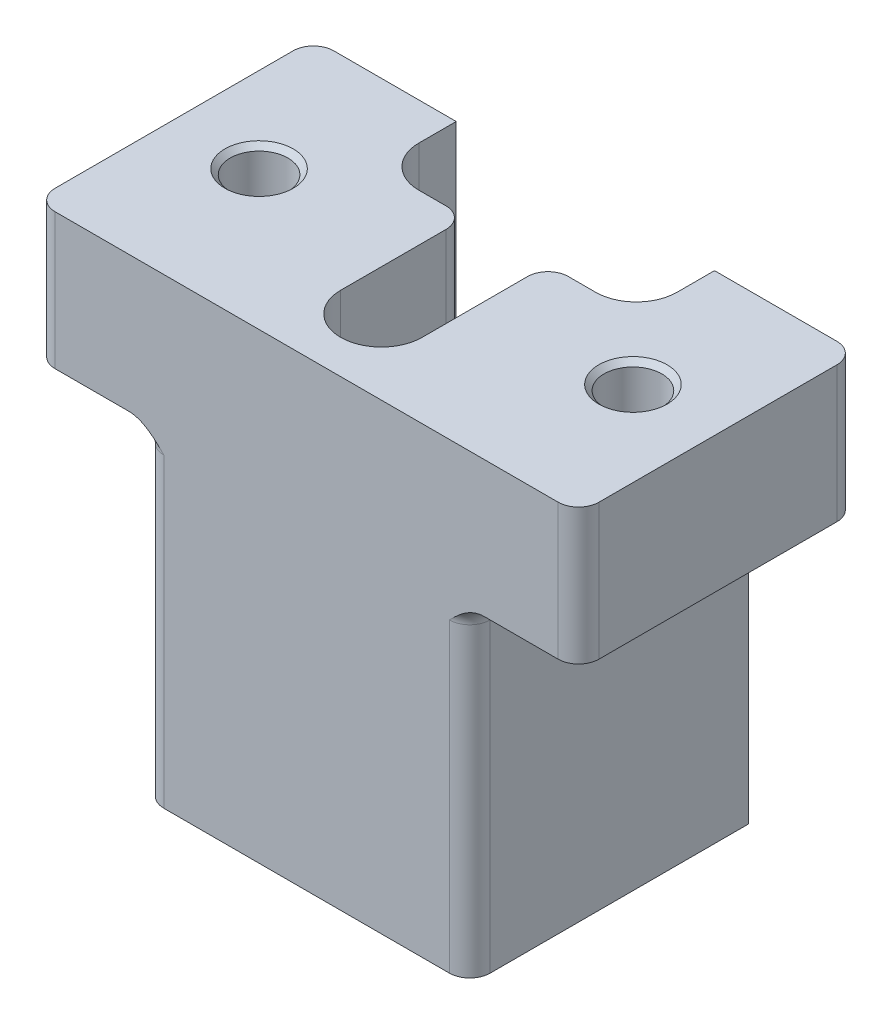
SolidWorks part; units mm, degrees
material "K110"
ref_plane "Front Plane" through (0, 0, 0) normal (0, 0, 1) x (1, 0, 0)
ref_plane "Top Plane" through (0, 0, 0) normal (0, 1, 0) x (1, 0, 0)
ref_plane "Right Plane" through (0, 0, 0) normal (1, 0, 0) x (0, 0, -1)
sketch "Sketch2" plane through (0, 0, 0) normal (0, 1, 0) x (1, 0, 0)
  line L0 (-19, 19.87) -> (-37, 19.87) construction
  line L1 (-40, -21.13) -> (40, -21.13)
  line L2 (-40, -21.13) -> (-40, 19.87)
  line L3 (-40, 19.87) -> (40, 19.87)
  line L4 (40, -21.13) -> (40, 19.87)
  line L5 (0, 0) -> (0, 19.87) construction
  line L7 (-37, -21.13) -> (37, -21.13) construction
  dimension "D2" = 80
extrude "Boss-Extrude1" add sketch "Sketch2" against normal blind 68
fillet "Fillet1" radius 3 4 edges at (-40, -34, -19.87) (-40, -34, 21.13) (40, -34, -19.87) (40, -34, 21.13)
sketch "Sketch5" plane through (0, -68, 0) normal (0, -1, 0) x (1, 0, 0)
  line L0 (19, -19.87) -> (24, -19.87) construction
  line L1 (19, -14.37) -> (19, -19.87) construction
  line L2 (9, -8.37) -> (13, -8.37) construction
  line L3 (6, 10.13) -> (6, -5.37) construction
  line L4 (-6, -5.37) -> (-6, 10.13) construction
  line L5 (-13, -8.37) -> (-9, -8.37) construction
  line L6 (-19, -19.87) -> (-19, -14.37) construction
  line L7 (-24, -19.87) -> (-19, -19.87) construction
  line L8 (-24, -19.87) -> (-24, 21.13) construction
  line L9 (24, 21.13) -> (-24, 21.13) construction
  line L10 (24, -19.87) -> (24, 21.13) construction
  line L11 (19, -19.87) -> (24, -19.87)
  line L12 (19, -14.37) -> (19, -19.87)
  line L13 (9, -8.37) -> (13, -8.37)
  line L14 (6, 10.13) -> (6, -5.37)
  line L15 (-6, -5.37) -> (-6, 10.13)
  line L16 (-13, -8.37) -> (-9, -8.37)
  line L17 (-19, -19.87) -> (-19, -14.37)
  line L18 (-24, -19.87) -> (-19, -19.87)
  line L19 (-24, -19.87) -> (-24, 21.13)
  line L20 (24, 21.13) -> (-24, 21.13)
  line L21 (24, -19.87) -> (24, 21.13)
  arc A0 (19, -14.37) -> (13, -8.37) centre (13, -14.37) ccw construction
  arc A1 (6, -5.37) -> (9, -8.37) centre (9, -5.37) ccw construction
  arc A2 (6, 10.13) -> (-6, 10.13) centre (0, 10.13) ccw construction
  arc A3 (-9, -8.37) -> (-6, -5.37) centre (-9, -5.37) ccw construction
  arc A4 (-13, -8.37) -> (-19, -14.37) centre (-13, -14.37) ccw construction
  arc A5 (19, -14.37) -> (13, -8.37) centre (13, -14.37) ccw
  arc A6 (6, -5.37) -> (9, -8.37) centre (9, -5.37) ccw
  arc A7 (6, 10.13) -> (-6, 10.13) centre (0, 10.13) ccw
  arc A8 (-9, -8.37) -> (-6, -5.37) centre (-9, -5.37) ccw
  arc A9 (-13, -8.37) -> (-19, -14.37) centre (-13, -14.37) ccw
extrude "Cut-Extrude2" cut sketch "Sketch5" against normal up to surface (48 mm away) flip side to cut
sketch "Sketch6" plane through (0, -68, 0) normal (0, -1, 0) x (1, 0, 0)
  line L0 (-19, -19.87) -> (-19, -14.37) construction
  line L1 (-13, -8.37) -> (-9, -8.37) construction
  line L2 (-6, -5.37) -> (-6, 10.13) construction
  line L3 (6, 10.13) -> (6, -5.37) construction
  line L4 (9, -8.37) -> (13, -8.37) construction
  line L5 (19, -14.37) -> (19, -19.87) construction
  line L6 (-13, -8.37) -> (-9, -8.37)
  line L7 (-6, -5.37) -> (-6, 10.13)
  line L8 (6, 10.13) -> (6, -5.37)
  line L9 (9, -8.37) -> (13, -8.37)
  line L10 (19, -14.37) -> (19, -19.87)
  line L11 (-19, -19.87) -> (-19, -14.37)
  line L12 (-19, -19.87) -> (19, -19.87)
  arc A0 (-9, -8.37) -> (-6, -5.37) centre (-9, -5.37) ccw construction
  arc A1 (-13, -8.37) -> (-19, -14.37) centre (-13, -14.37) ccw construction
  arc A2 (6, 10.13) -> (-6, 10.13) centre (0, 10.13) ccw construction
  arc A3 (6, -5.37) -> (9, -8.37) centre (9, -5.37) ccw construction
  arc A4 (19, -14.37) -> (13, -8.37) centre (13, -14.37) ccw construction
  arc A5 (-9, -8.37) -> (-6, -5.37) centre (-9, -5.37) ccw
  arc A6 (6, 10.13) -> (-6, 10.13) centre (0, 10.13) ccw
  arc A7 (6, -5.37) -> (9, -8.37) centre (9, -5.37) ccw
  arc A8 (19, -14.37) -> (13, -8.37) centre (13, -14.37) ccw
  arc A9 (-13, -8.37) -> (-19, -14.37) centre (-13, -14.37) ccw
extrude "Cut-Extrude3" cut sketch "Sketch6" against normal through all
fillet "Fillet2" radius 3 2 edges at (24, -44, 21.13) (-24, -44, 21.13)
fillet "Fillet3" radius 3 4 edges at (23.1213, -20, 20.2513) (24, -20, -0.87) (-23.1213, -20, 20.2513) (-24, -20, -0.87)
hole_wizard "M10 Tapped Hole1" positions "Sketch9" profile "Sketch8" tap size "M10" standard "ISO"
sketch "Sketch9" plane through (0, 0, 0) normal (0, 1, 0) x (1, 0, 0)
  line L11 (-40, -0.63) -> (40, -0.63) construction
  line L12 (-40, 16.87) -> (-40, -18.13) construction
  line L13 (40, -18.13) -> (40, 16.87) construction
  point P0 (27.5, -0.63)
  point P2 (-27.5, -0.63)
  dimension "D1" = 12.5
  dimension "D2" = 12.5
sketch "Sketch8" plane through (27.5, 0, 0.63) normal (1, 0, 0) x (0, 0, 1)
  line L0 (0, 0) -> (0, 19.5)
  line L1 (0, 19.5) -> (4.25, 16.9463)
  line L2 (4.25, 16.9463) -> (4.25, 0.775)
  line L3 (4.25, 0.775) -> (5.025, 0)
  line L5 (5.025, 0) -> (0, 0)
  line L6 (-4.25, 0.775) -> (-5.025, 0) construction
  line L10 (0, 19.5) -> (-4.25, 16.9463) construction
  line L11 (0, -6.35) -> (0, 107.95) construction
  dimension "Tap Drill Dia." = 8.5
  dimension "Tap Drill Depth" = 19.5
  dimension "Near C'Sink Dia." = 10.05
  dimension "Near C'Sink Angle" = 90
  dimension "Drill Angle" = 118
cosmetic thread "Hole Thread1"
cosmetic thread "Hole Thread2"
